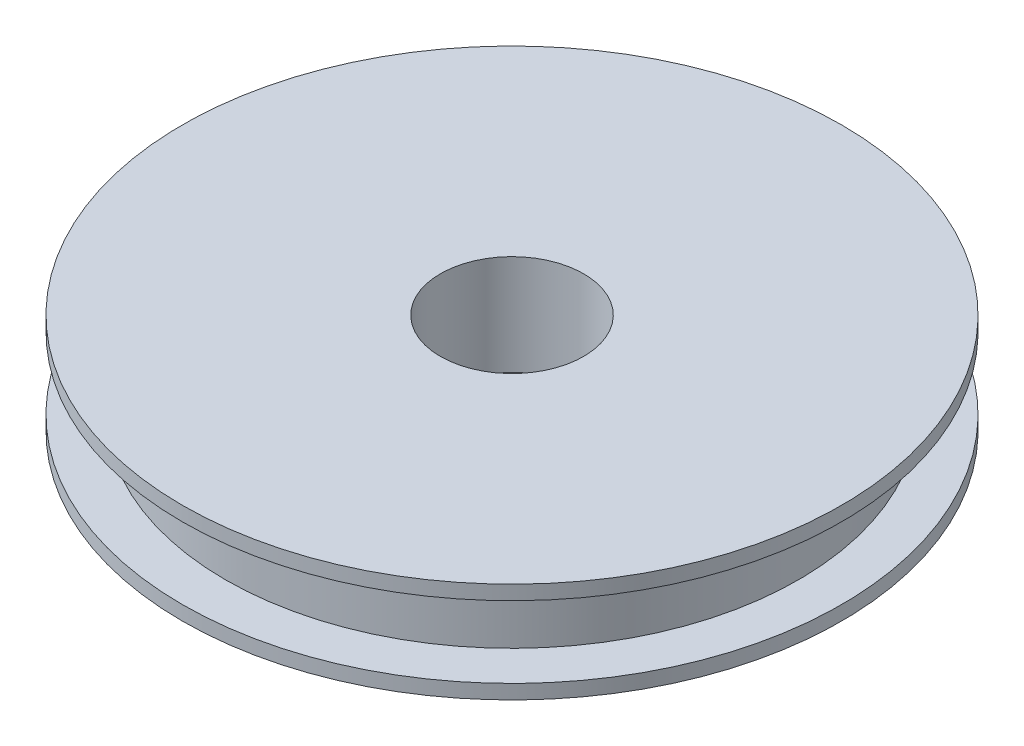
SolidWorks part; units mm, degrees
material "ABS PC"
ref_plane "Front Plane" through (0, 0, 0) normal (0, 0, 1) x (1, 0, 0)
ref_plane "Top Plane" through (0, 0, 0) normal (0, 1, 0) x (1, 0, 0)
ref_plane "Right Plane" through (0, 0, 0) normal (1, 0, 0) x (0, 0, -1)
sketch "Sketch1" plane through (0, 0, 0) normal (0, 1, 0) x (1, 0, 0)
  circle A0 centre (0, 0) radius 5
  circle A1 centre (0, 0) radius 20
  circle A2 centre (0, 0) radius 23
  dimension "D1" = 10
  dimension "D2" = 40
  dimension "D3" = 3
extrude "Boss-Extrude1" add sketch "Sketch1" along normal blind 5 contours A1 A0 region at (-19.4343, 0, 0)
extrude "Boss-Extrude2" add sketch "Sketch1<3>" against normal blind 1 contours A2 A1 | A1 A0 region at (-19.4343, 0, 0) region at (-22.3495, 0, 0)
sketch "Sketch1<3>" plane through (0, 0, 0) normal (0, 1, 0) x (1, 0, 0) same geometry as "Sketch1"
extrude "Boss-Extrude3" add sketch "Sketch1<4>" along normal blind 1 from surface contours A1 A0 | A2 A1 region at (-19.4343, 0, 0) region at (-22.3495, 0, 0) starting at face at (0, 5, 5)
sketch "Sketch1<4>" plane through (0, 0, 0) normal (0, 1, 0) x (1, 0, 0) same geometry as "Sketch1"
